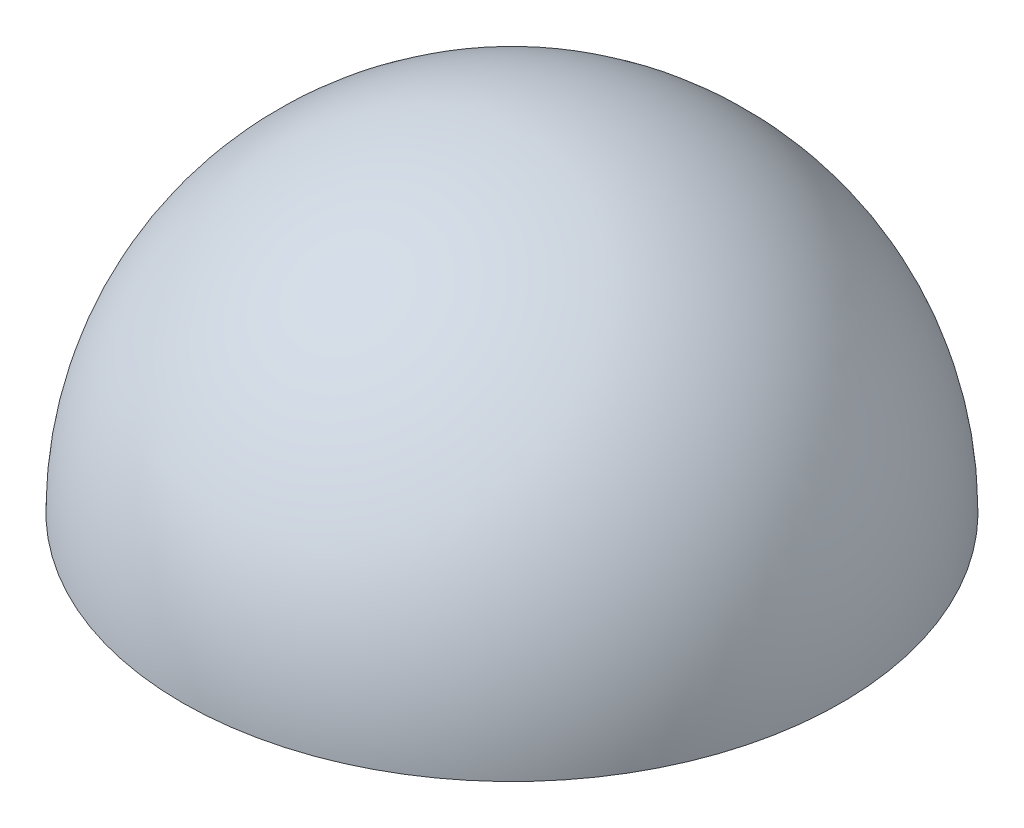
SolidWorks part; units mm, degrees
ref_plane "Front Plane" through (0, 0, 0) normal (0, 0, 1) x (1, 0, 0)
ref_plane "Top Plane" through (0, 0, 0) normal (0, 1, 0) x (1, 0, 0)
ref_plane "Right Plane" through (0, 0, 0) normal (1, 0, 0) x (0, 0, -1)
sketch "Sketch1" plane through (0, 0, 0) normal (0, 1, 0) x (1, 0, 0)
  circle A0 centre (0, 0) radius 5
  dimension "D1" = 10
extrude "Boss-Extrude1" add sketch "Sketch1" along normal blind 5
fillet "Fillet1" radius 5 1 edges at (0, 5, 5)
